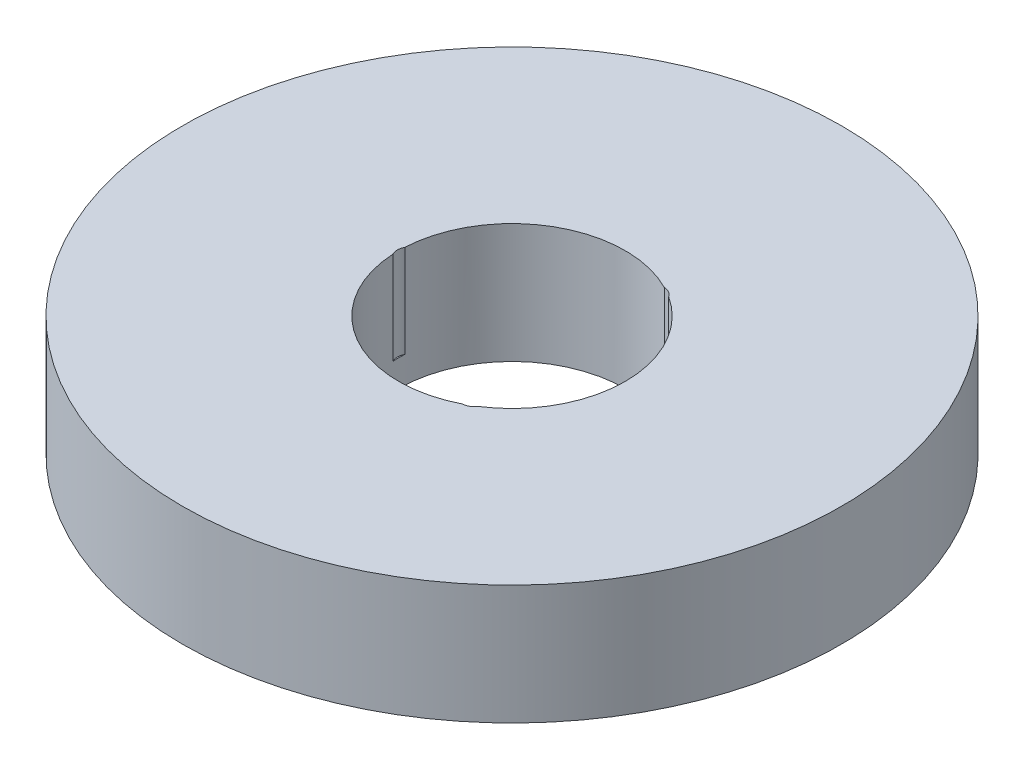
SolidWorks part; units mm, degrees
ref_plane "Front Plane" through (0, 0, 0) normal (0, 0, 1) x (1, 0, 0)
ref_plane "Top Plane" through (0, 0, 0) normal (0, 1, 0) x (1, 0, 0)
ref_plane "Right Plane" through (0, 0, 0) normal (1, 0, 0) x (0, 0, -1)
sketch "Sketch1" plane through (0, 0, 0) normal (0, 1, 0) x (1, 0, 0)
  circle A0 centre (0, 0) radius 80
  dimension "FLANGE_OD" = 160
extrude "Boss-Extrude1" add sketch "Sketch1" along normal blind 29
sketch "Sketch2" plane through (0, 0, 0) normal (0, 1, 0) x (1, 0, 0)
  circle A0 centre (0, 0) radius 27.5
  dimension "BORE_D" = 55
extrude "Cut-Extrude1" cut sketch "Sketch2" along normal through all
sketch "Sketch3" plane through (0, 29, 0) normal (0, 1, 0) x (1, 0, 0)
  circle A0 centre (0, 0) radius 24.62 construction
  circle A1 centre (-24.62, 0) radius 3.1849
  dimension "BOLT_D" = 6.3698
  dimension "BOLT_PCD" = 49.24
extrude "Cut-Extrude2" cut sketch "Sketch3" against normal blind 22.519
pattern_circular "CirPattern1" count 3 over 360 about axis through (0, 0, 0) along (0, 1, 0) of "Cut-Extrude2"
